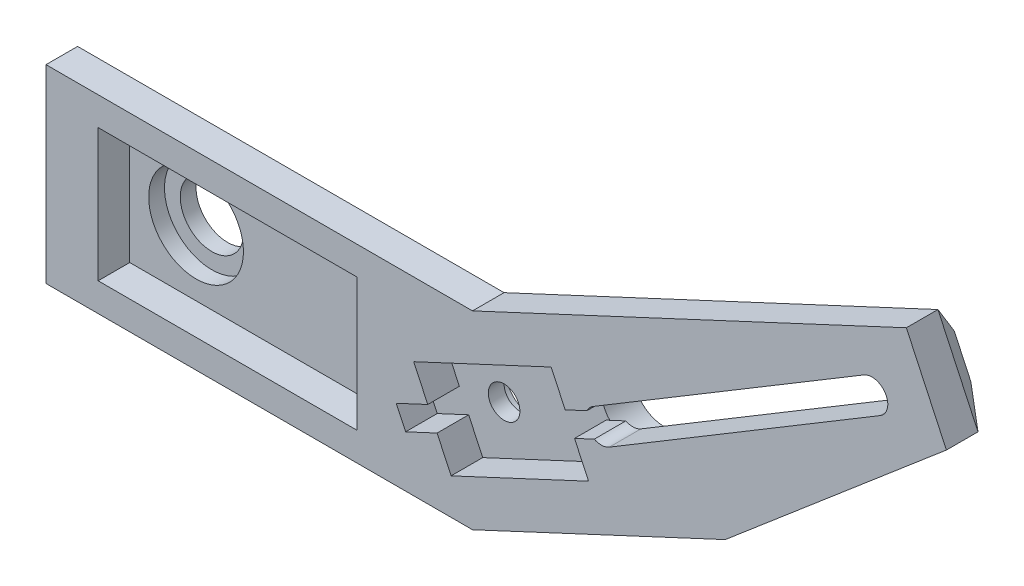
SolidWorks part; units mm, degrees
ref_plane "前视基准面" through (0, 0, 0) normal (0, 0, 1) x (1, 0, 0)
ref_plane "上视基准面" through (0, 0, 0) normal (0, 1, 0) x (1, 0, 0)
ref_plane "右视基准面" through (0, 0, 0) normal (1, 0, 0) x (0, 0, -1)
other "Configuration Table"
sketch "Sketch1" plane through (0, 0, 0) normal (0, 0, 1) x (1, 0, 0)
  line L1 (-28.75, -15) -> (28.75, -15)
  line L2 (-28.75, -15) -> (-28.75, 15)
  line L3 (-28.75, 15) -> (28.75, 15)
  line L4 (28.75, -15) -> (28.75, 15)
  line L5 (-28.75, -15) -> (28.75, 15) construction
  line L6 (-28.75, 15) -> (28.75, -15) construction
  point P0 (0, 0)
  dimension "D1" = 57.5
  dimension "D2" = 30
extrude "Boss-Extrude1" add sketch "Sketch1" along normal blind 30
sketch "Sketch2" plane through (0, 0, 30) normal (0, 0, 1) x (1, 0, 0)
  line L1 (-20.5, -10.5) -> (20.5, -10.5)
  line L2 (-20.5, -10.5) -> (-20.5, 10.5)
  line L3 (-20.5, 10.5) -> (20.5, 10.5)
  line L4 (20.5, -10.5) -> (20.5, 10.5)
  line L5 (-20.5, -10.5) -> (20.5, 10.5) construction
  line L6 (-20.5, 10.5) -> (20.5, -10.5) construction
  point P0 (0, 0)
  dimension "D1" = 41
  dimension "D2" = 21
extrude "Cut-Extrude1" cut sketch "Sketch2" against normal blind 25
ref_plane "Plane1" through (0, 0, 15) normal (0, 0, 1) x (1, 0, 0)
sketch "Sketch8" plane through (0, 0, 30) normal (0, 0, 1) x (1, 0, 0)
  line L0 (0, 0) -> (24.35, 0) construction
  line L1 (24.35, 0) -> (24.35, 6) construction
  line L2 (0, 0) -> (0, 15) construction
  line L3 (28.75, 15) -> (-28.75, 15) construction
  circle A0 centre (24.35, 6) radius 2
  circle A1 centre (24.35, -6) radius 2
  circle A2 centre (-24.35, -6) radius 2
  circle A3 centre (-24.35, 6) radius 2
  dimension "D3" = 4
  dimension "D1" = 6
  dimension "D2" = 24.35
extrude "Cut-Extrude6" cut sketch "Sketch8" against normal blind 10
sketch "Sketch10" plane through (0, 0, 5) normal (0, 0, 1) x (1, 0, 0)
  line L0 (0, 0) -> (-10, 0) construction
  circle A0 centre (-10, 0) radius 5
  dimension "D2" = 10
  dimension "D1" = 10
extrude "Cut-Extrude8" cut sketch "Sketch10" against normal blind 10
sketch "Sketch11" plane through (28.75, 0, 0) normal (1, 0, 0) x (0, 0, -1)
  line L0 (-30, 0) -> (0, 0) construction
  line L1 (-30, -15) -> (-30, 15) construction
  line L2 (0, 0) -> (-15, 0) construction
  line L3 (-15, -15) -> (-15, 15)
  line L4 (-30, 15) -> (0, 15) construction
  line L5 (-15, 15) -> (-11.75, 15)
  line L6 (-11.75, 15) -> (-11.75, 22.5)
  line L7 (-11.75, 22.5) -> (-18.25, 22.5)
  line L8 (-18.25, 22.5) -> (-18.25, 15)
  line L9 (-18.25, 15) -> (-15, 15)
  line L10 (7.5, 3.25) -> (0, 3.25)
  line L11 (0, 3.25) -> (0, 0)
  line L12 (0, -3.25) -> (7.5, -3.25)
  line L13 (0, 0) -> (0, -3.25)
  line L14 (7.5, -3.25) -> (7.5, 3.25)
  line L15 (-11.75, -22.5) -> (-11.75, -15)
  line L16 (-11.75, -15) -> (-15, -15)
  line L17 (-18.25, -15) -> (-18.25, -22.5)
  line L18 (-15, -15) -> (-18.25, -15)
  line L19 (-18.25, -22.5) -> (-11.75, -22.5)
  line L20 (-37.5, -3.25) -> (-30, -3.25)
  line L21 (-30, -3.25) -> (-30, 0)
  line L22 (-30, 3.25) -> (-37.5, 3.25)
  line L23 (-30, 0) -> (-30, 3.25)
  line L24 (-37.5, 3.25) -> (-37.5, -3.25)
  circle A0 centre (-15, 0) radius 7.5 construction
  point P12 (-15, 0)
  point P34 (-15, 0)
  line M5 (0, -15) -> (0, 15)
  line M6 (0, 15) -> (-30, 15)
  line M7 (-30, 15) -> (-30, -15)
  line M8 (-30, -15) -> (0, -15)
  dimension "D1" = 15
  dimension "D2" = 6.5
  dimension "D3" = 7.5
  dimension "D4" = 4
extrude "Boss-Extrude2" [suppressed] add sketch "Sketch11" against normal up to surface (8.25 mm away) contours L22 L24 L20 M7 | L17 L19 L15 M8 | L12 L14 L10 M5 | L7 L8 L6 M6
sketch "Sketch12" plane through (28.75, 0, 0) normal (1, 0, 0) x (0, 0, -1)
  line L20 (-36.5, 15) -> (-30, 15)
  line L21 (-30, -15) -> (-30, -21.5)
  line L22 (0, -15) -> (-11.75, -15)
  line L23 (0, 3.25) -> (0, 15)
  line L40 (0, -15) -> (0, 15)
  line L45 (0, 15) -> (-30, 15)
  line L50 (-30, 15) -> (-30, -15)
  line L55 (-30, -15) -> (0, -15)
  line L60 (0, -15) -> (0, 15)
  line L65 (0, 15) -> (-30, 15)
  line L70 (-30, 15) -> (-30, -15)
  line L75 (-30, -15) -> (0, -15)
  dimension "D1" = 0
extrude "Boss-Extrude3" [suppressed] add sketch "Sketch12" along normal blind 30
sketch "Sketch13" plane through (0, 0, 30) normal (0, 0, 1) x (1, 0, 0)
  line L0 (28.75, 15) -> (38.75, 15)
  line L1 (38.75, 15) -> (107.4107, 47.017)
  line L3 (113.75, 33.4224) -> (78.75, 3.6523)
  line L4 (78.75, 3.6523) -> (38.75, -15)
  line L5 (38.75, -15) -> (28.75, -15)
  line L6 (-28.75, -15) -> (28.75, -15) construction
  line L7 (38.75, 15) -> (38.75, -15) construction
  line L8 (38.75, -15) -> (93.0307, -15) construction
  line L9 (78.75, 3.6523) -> (97.9021, 3.6523) construction
  line L10 (38.75, 15) -> (83.4484, 15) construction
  line L11 (28.75, -15) -> (28.75, 15)
  line L12 (107.4107, 47.017) -> (113.75, 33.4224)
  dimension "D1" = 10
  dimension "D2" = 25
  dimension "D3" = 40
  dimension "D4" = 25
  dimension "D5" = 15
  dimension "D6" = 75
extrude "Boss-Extrude4" add sketch "Sketch13" against normal blind 30
sketch "Sketch16" plane through (1.1757, -2.5212, 0) normal (-0.4226, 0.9063, 0) x (0.9063, 0.4226, 0)
  line L0 (117.2174, -15) -> (97.2174, -15) construction
  line L1 (117.2174, 0) -> (117.2174, -30) construction
  line L2 (-55, -15) -> (55, -15) construction
  line L3 (97.2174, -15) -> (74.7174, -15) construction
  line L4 (67.2174, -15) -> (82.2174, -15) construction
  line L5 (67.2174, -12.5) -> (82.2174, -12.5)
  line L6 (67.2174, -17.5) -> (82.2174, -17.5)
  circle A0 centre (97.2174, -15) radius 5
  arc A1 (67.2174, -12.5) -> (67.2174, -17.5) centre (67.2174, -15) ccw
  arc A2 (82.2174, -17.5) -> (82.2174, -12.5) centre (82.2174, -15) ccw
  point P10 (74.7174, -15)
  dimension "D1" = 10
  dimension "D4" = 2.5
  dimension "D2" = 20
  dimension "D3" = 15
  dimension "D5" = 22.5
extrude "Cut-Extrude10" cut sketch "Sketch16" against normal blind 30
chamfer "Chamfer5" distance 5 angle 45 13 edges at (-28.75, 0, 0) (5, -15, 0) (58.75, -5.6738, 0) (96.25, 18.5374, 0) (110.5804, 40.2197, 0) (73.0804, 31.0085, 0) (5, 15, 0) (5, -15, 30) (58.75, -5.6738, 30) (96.25, 18.5374, 30) (73.0804, 31.0085, 30) (5, 15, 30) (110.5804, 40.2197, 30)
sketch "Sketch20" plane through (0, 0, 5) normal (0, 0, 1) x (1, 0, 0)
  circle A0 centre (-10, 0) radius 7.5
  dimension "D1" = 15
extrude "Cut-Extrude13" cut sketch "Sketch20" against normal blind 2.5
sketch "Sketch30" plane through (0, 15, 0) normal (0, 1, 0) x (1, 0, 0)
  line L0 (-28.75, -30) -> (-28.75, -10)
  line L1 (-28.75, -25) -> (-28.75, -5) construction
  line L2 (-28.75, -10) -> (113.75, -10)
  line L3 (113.75, -5) -> (113.75, -25) construction
  line L4 (113.75, -10) -> (113.75, -30)
  line L5 (113.75, -30) -> (-28.75, -30)
  dimension "D1" = 20
extrude "Cut-Extrude16" cut sketch "Sketch30" against normal through all both and the other way through all
sketch "Sketch31" plane through (0, 0, 10) normal (0, 0, 1) x (1, 0, 0)
  line L2 (38.75, -15) -> (38.75, 0) construction
  line L3 (38.75, 0) -> (43.2815, 2.1131) construction
  line L4 (38.75, -15) -> (78.75, 3.6523) construction
  line L5 (28.1607, -6.8688) -> (59.8815, 7.9229)
  line L6 (35.3642, -9.3025) -> (57.1156, 0.8404)
  line L7 (35.3642, -9.3025) -> (29.4475, 3.3858)
  line L8 (29.4475, 3.3858) -> (51.1989, 13.5287)
  line L9 (57.1156, 0.8404) -> (51.1989, 13.5287)
  line L10 (35.3642, -9.3025) -> (51.1989, 13.5287) construction
  line L11 (29.4475, 3.3858) -> (57.1156, 0.8404) construction
  line L12 (28.1607, -6.8688) -> (26.6816, -3.6967)
  line L13 (59.8815, 7.9229) -> (58.4023, 11.0949)
  line L14 (26.6816, -3.6967) -> (58.4023, 11.0949)
  line L15 (28.1607, -6.8688) -> (58.4023, 11.0949) construction
  line L16 (59.8815, 7.9229) -> (26.6816, -3.6967) construction
  line L17 (43.2815, 2.1131) -> (59.1419, 9.5089) construction
  point P15 (0, 0)
  point P17 (36.0536, 0)
  dimension "D1" = 24
  dimension "D2" = 14
  dimension "D3" = 5
  dimension "D4" = 90
  dimension "D5" = 35
  dimension "D6" = 3.5
  dimension "D7" = 15
extrude "Cut-Extrude17" cut sketch "Sketch31" against normal blind 5 contours L7 L14 L9 L8 | L6 L9 L5 L7 | L14 L12 L5 L7 | L14 L7 L5 L9 | L14 L9 L5 L13 region at (29.9135, -4.1205, 10) region at (43.2815, 2.1131, 10) region at (45.1305, -1.852, 10) region at (56.6496, 8.3467, 10) region at (41.4326, 6.0782, 10)
sketch "Sketch33" plane through (0, 0, 0) normal (0, 0, 1) x (1, 0, 0)
  line L0 (110.5804, 40.2197) -> (125.3057, 40.2197) construction
  line L1 (113.75, 33.4224) -> (107.4107, 47.017) construction
  line L4 (110.5804, 40.2197) -> (101.9744, 35.0487) construction
  line L6 (59.116, 9.2968) -> (101.9744, 35.0487) construction
  line L7 (57.8284, 11.4397) -> (100.6868, 37.1916)
  line L8 (60.4036, 7.1539) -> (103.262, 32.9058)
  arc A1 (57.8284, 11.4397) -> (60.4036, 7.1539) centre (59.116, 9.2968) ccw
  arc A2 (103.262, 32.9058) -> (100.6868, 37.1916) centre (101.9744, 35.0487) ccw
  point P0 (110.5804, 40.2197)
  point P4 (80.5452, 22.1728)
  dimension "D1" = 2.5
  dimension "D2" = 50
  dimension "D3" = 10.04
  dimension "D4" = 149
extrude "Cut-Extrude19" cut sketch "Sketch33" along normal through all contours L8 A2 L7 A1 region at (80.5452, 22.1728, 0)
sketch "Sketch34" plane through (0, 0, 0) normal (0, 0, -1) x (-1, 0, 0)
  line L0 (-101.9744, 35.0487) -> (-59.116, 9.2968) construction
  line L1 (-99.3992, 39.3346) -> (-56.5408, 13.5827)
  line L2 (-104.5496, 30.7629) -> (-61.6912, 5.011)
  arc A0 (-99.3992, 39.3346) -> (-104.5496, 30.7629) centre (-101.9744, 35.0487) ccw
  arc A1 (-61.6912, 5.011) -> (-56.5408, 13.5827) centre (-59.116, 9.2968) ccw
  point P4 (-80.5452, 22.1728)
  dimension "D1" = 5
extrude "Cut-Extrude20" cut sketch "Sketch34" against normal blind 5
sketch "Sketch35" plane through (0, 0, 0) normal (0, 0, -1) x (-1, 0, 0)
  line L0 (-38.75, -15) -> (-38.75, 15) construction
  line L1 (-38.75, 15) -> (-38.75, 0) construction
  circle A0 centre (-38.75, 0) radius 2.5
  dimension "D1" = 5
extrude "Cut-Extrude21" cut sketch "Sketch35" against normal blind 5
sketch "Sketch36" plane through (0, 0, 0) normal (0, 0, -1) x (-1, 0, 0)
  circle A0 centre (-38.75, 0) radius 5
  dimension "D1" = 10
extrude "Cut-Extrude22" cut sketch "Sketch36" against normal blind 2.5
